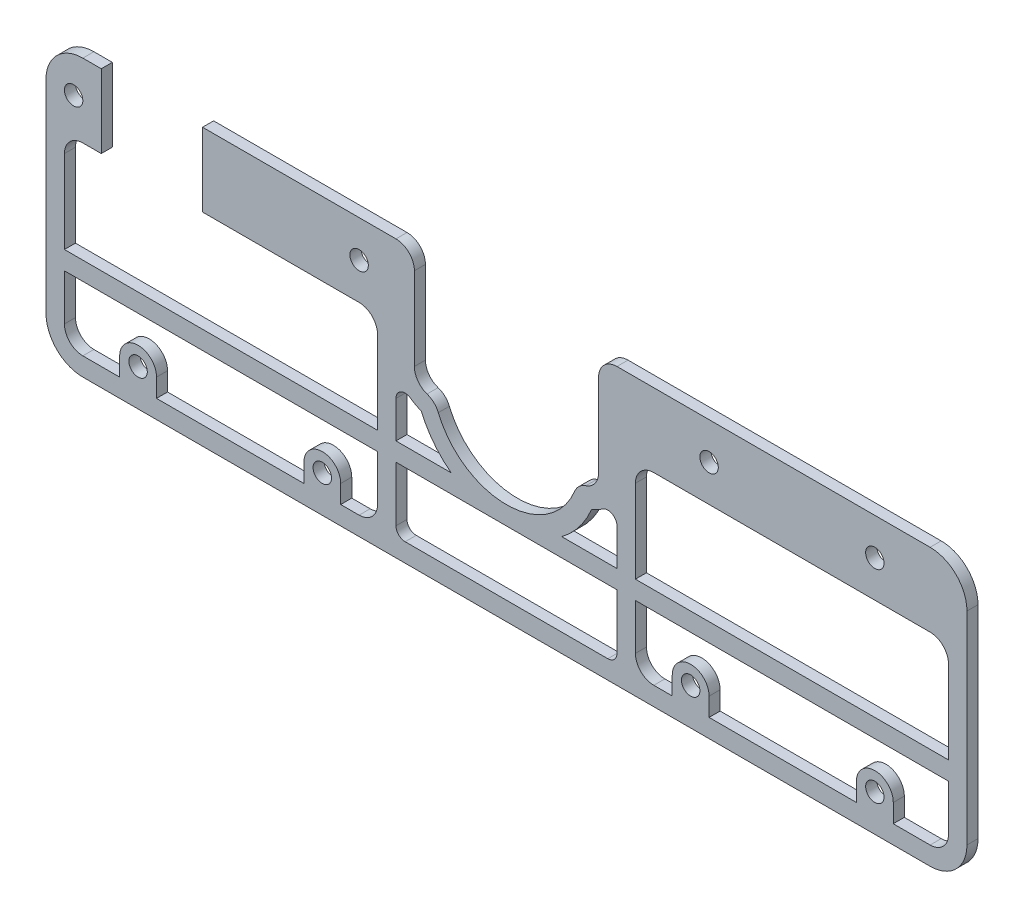
SolidWorks part; units mm, degrees
ref_plane "Front Plane" through (0, 0, 0) normal (0, 0, 1) x (1, 0, 0)
ref_plane "Top Plane" through (0, 0, 0) normal (0, 1, 0) x (1, 0, 0)
ref_plane "Right Plane" through (0, 0, 0) normal (1, 0, 0) x (0, 0, -1)
sketch "Sketch1" plane through (0, 0, 0) normal (0, 0, 1) x (1, 0, 0)
  line L0 (-40, 20) -> (-40, 55) construction
  line L4 (-250, -55) -> (-250, 3.1783)
  line L8 (-50, 75) -> (-230, 75) construction
  line L17 (0, -20) -> (0, -40)
  line L25 (0, -65) -> (0, -75)
  line L26 (0, 75) -> (0, -75) construction
  line L27 (-50, 95) -> (50, 95) construction
  line L34 (0, -75) -> (-230, -75)
  line L156 (-50, 75) -> (-230, 75) construction
  line L161 (0, -40) -> (0, -65)
  line L165 (-164.3309, 75) -> (-60, 75)
  line L167 (-230, 75) -> (-220, 75)
  line L171 (-250, 3.1783) -> (-250, 55)
  line L172 (-220, 75) -> (-164.3309, 75)
  line L173 (-50, 65) -> (-50, 20)
  arc A0 (-40, 20) -> (0, -20) centre (0, 20) ccw construction
  circle A1 centre (0, 20) radius 30 construction
  arc A4 (-230, -75) -> (-250, -55) centre (-230, -55) cw
  arc A5 (-250, 55) -> (-230, 75) centre (-230, 55) cw
  arc A124 (0, -20) -> (-37, 4.8013) centre (0, 20) cw
  arc A125 (-60, 75) -> (-50, 65) centre (-60, 65) cw
  arc A126 (-43.125, 10.5008) -> (-50, 20) centre (-40, 20) cw
  arc A127 (-37, 4.8013) -> (-43.125, 10.5008) centre (-46.25, 1.0016) ccw
  point P0 (0, 0)
  point P10 (-50, 10)
  point P11 (0, 50)
  point P30 (-40, 75)
  point P45 (0, -30)
  point P74 (0, 95)
  dimension "D3" = 80
  dimension "D4" = 60
  dimension "D6" = 55
  dimension "D7" = 75
  dimension "D10" = 10
  dimension "D11" = 20
  dimension "D8" = 10
  dimension "D5" = 10
  dimension "D9" = 20
  dimension "D13" = 210
  dimension "D16" = 100
  dimension "D17" = 20
  dimension "D26" = 250
extrude "Boss-Extrude1" add sketch "Sketch1" along normal blind 6
mirror "Mirror1" about plane through (0, -20, 6) normal (-1, 0, 0) of "Boss-Extrude1"
sketch "Sketch4" plane through (0, 0, 6) normal (0, 0, 1) x (1, 0, 0)
  line L0 (-230, -75) -> (230, -75) construction
  line L1 (-70, 25.101) -> (-70, -54.899)
  line L2 (-50, 20) -> (-50, 65) construction
  line L7 (-240, -55) -> (-240, 25.101)
  line L8 (-250, 55) -> (-250, -55) construction
  line L11 (-110, 35.101) -> (-80, 35.101)
  line L12 (-110, 35.101) -> (-140, 35.101)
  line L13 (-230, 35.101) -> (-140, 35.101)
  line L15 (-230, -65) -> (-210, -65)
  line L16 (-210, -65) -> (-210, -55)
  line L17 (-190, -55) -> (-190, -65)
  line L18 (-190, -65) -> (-110, -65)
  line L19 (-110, -65) -> (-110, -55)
  line L20 (-90, -55) -> (-90, -64.899)
  line L21 (-90, -64.899) -> (-80, -64.899)
  circle A1 centre (-200, -55) radius 5
  circle A2 centre (-100, -55) radius 5
  arc A6 (-230, -65) -> (-240, -55) centre (-230, -55) cw
  arc A12 (-210, -55) -> (-190, -55) centre (-200, -55) cw
  arc A13 (-110, -55) -> (-90, -55) centre (-100, -55) cw
  arc A14 (-240, 25.101) -> (-230, 35.101) centre (-230, 25.101) cw
  arc A15 (-70, -54.899) -> (-80, -64.899) centre (-80, -54.899) cw
  arc A16 (-70, 25.101) -> (-80, 35.101) centre (-80, 25.101) ccw
  point P0 (0, -75)
  dimension "D13" = 10
  dimension "D17" = 10
  dimension "D2" = 10
  dimension "D3" = 200
  dimension "D4" = 100
  dimension "D7" = 20
  dimension "D9" = 10
  dimension "D11" = 20
  dimension "D16" = 80
extrude "Cut-Extrude2" cut sketch "Sketch4" against normal through all contours L7 A6 L15 L16 | L13 | L17 L18 L19 | L20 L21 A15 L1 A16 L11 | A1 | A2 region at (-155.2296, -13.1384, 6) region at (-200, -55, 6) region at (-100, -55, 6)
mirror "Mirror2" about plane through (0, 0, 0) normal (1, 0, 0) of "Cut-Extrude2"
sketch "Sketch8" plane through (0, 0, 6) normal (0, 0, 1) x (1, 0, 0)
  line L0 (-60, 0) -> (-60, -64.899)
  line L2 (-60, -64.899) -> (60, -64.899)
  line L3 (60, -64.899) -> (60, 0)
  line L4 (-90, -64.899) -> (-80, -64.899) construction
  arc A0 (43.125, 10.5008) -> (50, 20) centre (40, 20) ccw construction
  arc A1 (43.125, 10.5008) -> (37, 4.8013) centre (46.25, 1.0016) ccw construction
  arc A2 (-37, 4.8013) -> (-43.125, 10.5008) centre (-46.25, 1.0016) ccw construction
  arc A3 (-50, 20) -> (-43.125, 10.5008) centre (-40, 20) ccw construction
  arc A4 (-37, 4.8013) -> (37, 4.8013) centre (0, 20) ccw construction
  arc A5 (43.125, 10.5008) -> (50, 20) centre (40, 20) ccw construction
  arc A6 (43.125, 10.5008) -> (37, 4.8013) centre (46.25, 1.0016) ccw construction
  arc A7 (-37, 4.8013) -> (-43.125, 10.5008) centre (-46.25, 1.0016) ccw construction
  arc A8 (-50, 20) -> (-43.125, 10.5008) centre (-40, 20) ccw construction
  arc A9 (-37, 4.8013) -> (37, 4.8013) centre (0, 20) ccw construction
  arc A10 (-52, 4) -> (-46.25, 1.0016) centre (-40, 20) ccw
  arc A11 (-46.25, 1.0016) -> (-46.25, 1.0016) centre (-46.25, 1.0016) ccw
  arc A12 (-46.25, 1.0016) -> (46.25, 1.0016) centre (0, 20) ccw
  arc A13 (46.25, 1.0016) -> (46.25, 1.0016) centre (46.25, 1.0016) ccw
  arc A14 (46.25, 1.0016) -> (52, 4) centre (40, 20) ccw
  arc A15 (46.25, 1.0016) -> (60, 20) centre (40, 20) ccw construction
  arc A16 (60, 0) -> (52, 4) centre (55, 0) ccw
  arc A17 (-60, 20) -> (-46.25, 1.0016) centre (-40, 20) ccw construction
  arc A18 (-60, 0) -> (-52, 4) centre (-55, 0) cw
  dimension "D2" = 5
  dimension "D1" = 10
extrude "Cut-Extrude5" cut sketch "Sketch8" against normal through all
fillet "Fillet5" radius 5 1 edges at (-60, -64.899, 3)
fillet "Fillet6" radius 5 1 edges at (60, -64.899, 3)
sketch "Sketch9" plane through (0, 0, 0) normal (0, 0, -1) x (-1, 0, 0)
  line L0 (-250, 55) -> (-250, -55) construction
  line L2 (250, 55) -> (250, -55) construction
  line L3 (165, 75) -> (165, 35.101)
  line L4 (60, 75) -> (230, 75) construction
  line L5 (230, 35.101) -> (80, 35.101) construction
  line L6 (165, 35.101) -> (220, 35.101)
  line L7 (220, 35.101) -> (220, 75)
  line L8 (220, 75) -> (165, 75)
  circle A0 centre (-200, 55) radius 5
  circle A1 centre (-110, 55) radius 5
  circle A2 centre (80, 55) radius 5
  circle A3 centre (235, 55) radius 5
  dimension "D1" = 10
  dimension "D3" = 90
  dimension "D4" = 15
  dimension "D5" = 170
  dimension "D7" = 20
  dimension "D2" = 50
  dimension "D6" = 55
  dimension "D8" = 30
extrude "Cut-Extrude6" cut sketch "Sketch9" against normal through all
sketch "Sketch10" plane through (0, 0, 0) normal (0, 0, -1) x (-1, 0, 0)
  line L0 (-250, -20) -> (250, -20)
  line L1 (-250, 55) -> (-250, -55) construction
  line L2 (250, 55) -> (250, -55) construction
  line L3 (250, -20) -> (250, -30)
  line L4 (250, -30) -> (-250, -30)
  line L5 (-250, -30) -> (-250, -20)
  arc A0 (-37, 4.8013) -> (37, 4.8013) centre (0, 20) ccw construction
  arc A1 (-46.25, 1.0016) -> (46.25, 1.0016) centre (0, 20) ccw construction
extrude "Boss-Extrude2" add sketch "Sketch10" against normal up to surface (6 mm away) up to face at (195, 55, 6)
